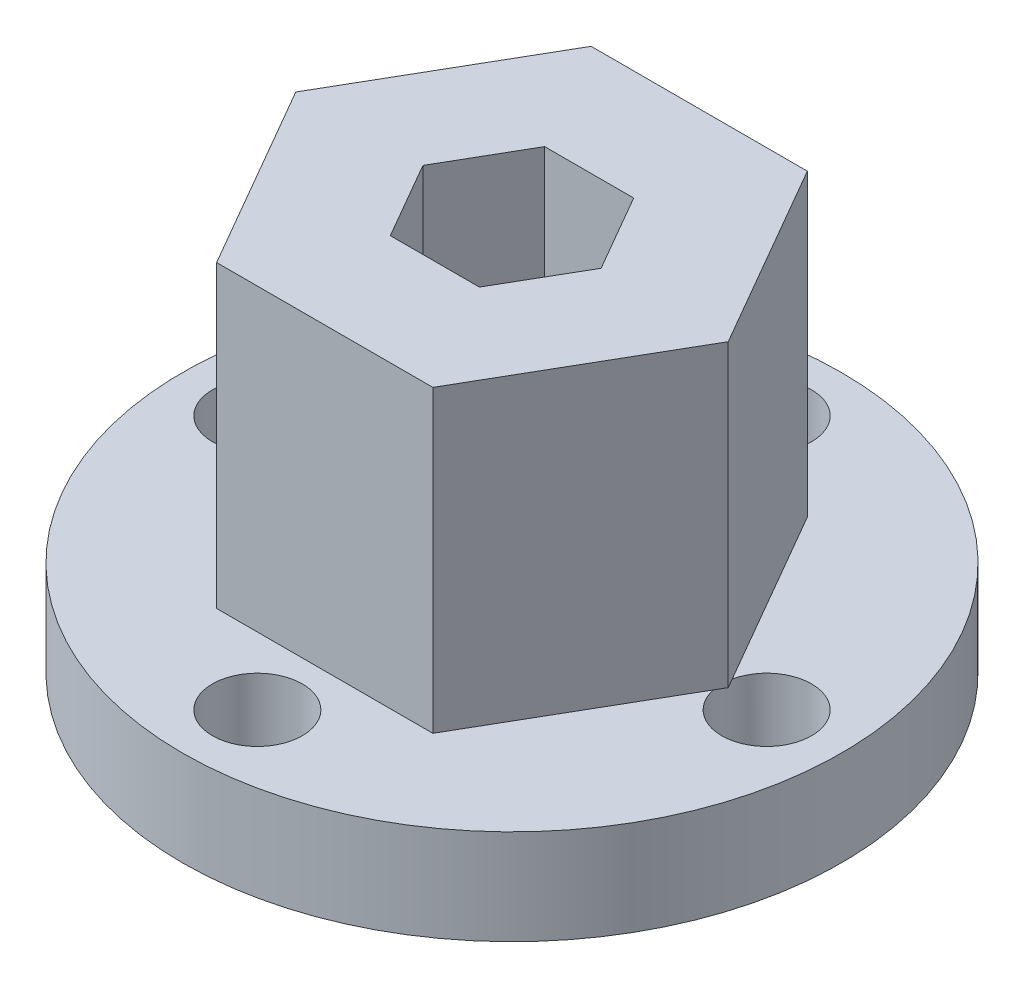
SolidWorks part; units mm, degrees
ref_plane "Front" through (0, 0, 0) normal (0, 0, 1) x (1, 0, 0)
ref_plane "Top" through (0, 0, 0) normal (0, 1, 0) x (1, 0, 0)
ref_plane "Right" through (0, 0, 0) normal (1, 0, 0) x (0, 0, -1)
sketch "Sketch1" plane through (0, 0, 0) normal (0, 1, 0) x (1, 0, 0)
  circle A0 centre (0, 0) radius 11
  dimension "D1" = 22
extrude "Boss-Extrude1" add sketch "Sketch1" along normal blind 3.175
sketch "Sketch2" plane through (0, 3.175, 0) normal (0, 1, 0) x (1, 0, 0)
  line L1 (3.6084, -6.25) -> (7.2169, 0)
  line L2 (7.2169, 0) -> (3.6084, 6.25)
  line L3 (3.6084, 6.25) -> (-3.6084, 6.25)
  line L4 (-3.6084, 6.25) -> (-7.2169, 0)
  line L5 (-7.2169, 0) -> (-3.6084, -6.25)
  line L6 (-3.6084, -6.25) -> (3.6084, -6.25)
  circle A0 centre (0, 0) radius 6.25 construction
  dimension "D1" = 12.5
extrude "Boss-Extrude2" add sketch "Sketch2" along normal blind 10 contours L6 L1 L2 L3 L4 L5
sketch "Sketch3" plane through (0, 13.175, 0) normal (0, 1, 0) x (1, 0, 0)
  line L1 (1.4867, -2.575) -> (2.9734, 0)
  line L2 (2.9734, 0) -> (1.4867, 2.575)
  line L3 (1.4867, 2.575) -> (-1.4867, 2.575)
  line L4 (-1.4867, 2.575) -> (-2.9734, 0)
  line L5 (-2.9734, 0) -> (-1.4867, -2.575)
  line L6 (-1.4867, -2.575) -> (1.4867, -2.575)
  circle A0 centre (0, 0) radius 2.575 construction
  dimension "D1" = 5.15
extrude "Cut-Extrude2" cut sketch "Sketch3" against normal blind 28
sketch "Sketch6" plane through (0, 3.175, 0) normal (0, 1, 0) x (1, 0, 0)
  circle A0 centre (0, 8.5) radius 1.5
  circle A1 centre (0, 0) radius 11 construction
  circle A2 centre (8.5, 0) radius 1.5
  circle A3 centre (0, -8.5) radius 1.5
  circle A4 centre (-8.5, 0) radius 1.5
  point P13 (0, 0)
  dimension "D1" = 8.5
  dimension "D2" = 4
extrude "Cut-Extrude3" cut sketch "Sketch6" against normal blind 8
